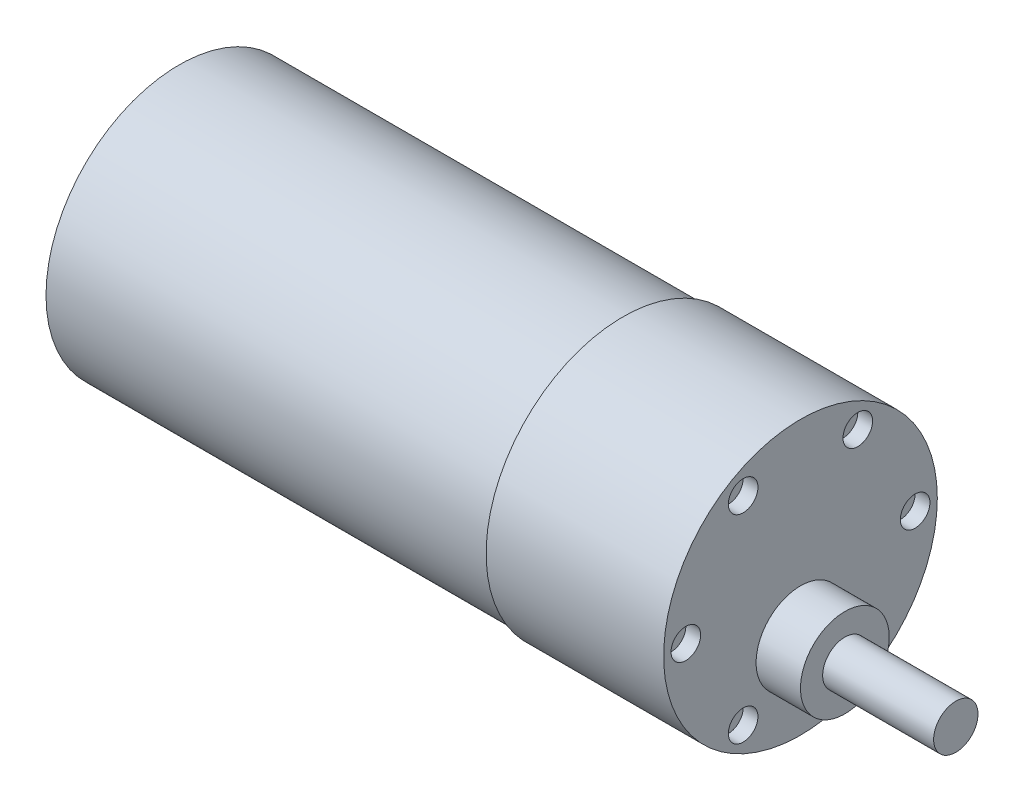
SolidWorks part; units mm, degrees
ref_plane "Front Plane" through (0, 0, 0) normal (0, 0, 1) x (1, 0, 0)
ref_plane "Top Plane" through (0, 0, 0) normal (0, 1, 0) x (1, 0, 0)
ref_plane "Right Plane" through (0, 0, 0) normal (1, 0, 0) x (0, 0, -1)
sketch "Sketch1" plane through (0, 0, 0) normal (1, 0, 0) x (0, 0, -1)
  circle A0 centre (0, 0) radius 18.5
  circle A1 centre (0, -7) radius 6 construction
  circle A2 centre (-15.5, 0) radius 2 construction
  circle A3 centre (-7.75, 13.4234) radius 2 construction
  circle A4 centre (7.75, 13.4234) radius 2 construction
  circle A5 centre (15.5, 0) radius 2 construction
  circle A6 centre (7.75, -13.4234) radius 2 construction
  circle A7 centre (-7.75, -13.4234) radius 2 construction
  point P19 (0, 0)
  dimension "D1" = 37
  dimension "D3" = 12
  dimension "D4" = 15.5
  dimension "D5" = 4
  dimension "D2" = 7
  dimension "D6" = 6
extrude "Boss-Extrude1" add sketch "Sketch1" against normal blind 24
sketch "Sketch2" plane through (-24, 0, 0) normal (-1, 0, 0) x (0, 0, 1)
  circle A0 centre (0, 0) radius 18
extrude "Boss-Extrude2" add sketch "Sketch2" along normal blind 60
sketch "Sketch3" plane through (0, 0, 0) normal (1, 0, 0) x (0, 0, -1)
  line L0 (0, 0) -> (0, -7) construction
  circle A1 centre (0, -7) radius 6
  dimension "D2" = 12
  dimension "D1" = 7
extrude "Boss-Extrude3" add sketch "Sketch3" along normal blind 6
sketch "Sketch4" plane through (6, 0, 0) normal (1, 0, 0) x (0, 0, -1)
  circle A0 centre (0, -7) radius 3
  dimension "D1" = 6
extrude "Boss-Extrude4" add sketch "Sketch4" along normal blind 15
sketch "Sketch5" plane through (0, 0, 0) normal (1, 0, 0) x (0, 0, -1)
  line L0 (-15.5, 0) -> (0, 0) construction
  circle A0 centre (-15.5, 0) radius 2
  circle A1 centre (-7.75, 13.4234) radius 2
  circle A2 centre (7.75, 13.4234) radius 2
  circle A3 centre (15.5, 0) radius 2
  circle A4 centre (7.75, -13.4234) radius 2
  circle A5 centre (-7.75, -13.4234) radius 2
  point P15 (0, 0)
  dimension "D2" = 4
  dimension "D1" = 15.5
  dimension "D3" = 6
extrude "Cut-Extrude1" cut sketch "Sketch5" against normal blind 2
